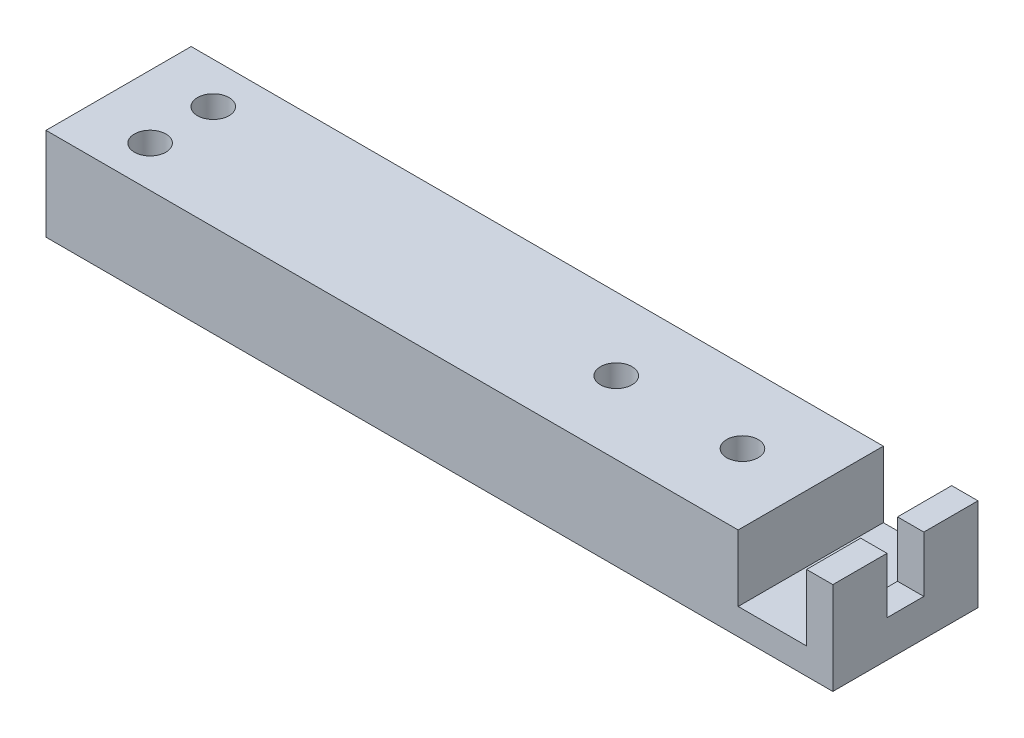
SolidWorks part; units mm, degrees
ref_plane "Front Plane" through (0, 0, 0) normal (0, 0, 1) x (1, 0, 0)
ref_plane "Top Plane" through (0, 0, 0) normal (0, 1, 0) x (1, 0, 0)
ref_plane "Right Plane" through (0, 0, 0) normal (1, 0, 0) x (0, 0, -1)
sketch "Sketch1" plane through (0, 0, 0) normal (0, 1, 0) x (1, 0, 0)
  line L1 (-37.4, -6.9) -> (37.4, -6.9)
  line L2 (-37.4, -6.9) -> (-37.4, 6.9)
  line L3 (-37.4, 6.9) -> (37.4, 6.9)
  line L4 (37.4, -6.9) -> (37.4, 6.9)
  line L5 (-37.4, -6.9) -> (37.4, 6.9) construction
  line L6 (-37.4, 6.9) -> (37.4, -6.9) construction
  point P0 (0, 0)
  dimension "D1" = 13.8
  dimension "D2" = 74.8
extrude "Boss-Extrude1" add sketch "Sketch1" along normal blind 8.8
sketch "Sketch2" plane through (0, 8.8, 0) normal (0, 1, 0) x (1, 0, 0)
  line L0 (-37.4, -6.9) -> (37.4, -6.9) construction
  line L1 (34.9, -6.9) -> (28.4, -6.9)
  line L2 (34.9, -6.9) -> (34.9, 6.9)
  line L3 (34.9, 6.9) -> (28.4, 6.9)
  line L4 (28.4, -6.9) -> (28.4, 6.9)
  line L5 (37.4, 6.9) -> (-37.4, 6.9) construction
  line L6 (37.4, -6.9) -> (37.4, 6.9) construction
  dimension "D1" = 2.5
  dimension "D2" = 6.5
extrude "Cut-Extrude1" cut sketch "Sketch2" against normal offset from surface (6.3 mm away) 2.5 up to face at (0, 0, 0)
sketch "Sketch3" plane through (37.4, 0, 0) normal (1, 0, 0) x (0, 0, -1)
  line L0 (-6.9, 8.8) -> (6.9, 8.8) construction
  line L1 (1.75, 8.8) -> (-1.75, 8.8)
  line L2 (1.75, 8.8) -> (1.75, 3.5)
  line L3 (1.75, 3.5) -> (-1.75, 3.5)
  line L4 (-1.75, 8.8) -> (-1.75, 3.5)
  line L5 (-6.9, 0) -> (6.9, 0) construction
  point P8 (0, 0)
  point P9 (0, 8.8)
  dimension "D1" = 3.5
  dimension "D2" = 3.5
extrude "Cut-Extrude2" cut sketch "Sketch3" against normal blind 2.8
sketch "Sketch4" plane through (0, 8.8, 0) normal (0, 1, 0) x (1, 0, 0)
  line L0 (-37.4, 6.9) -> (-37.4, -6.9) construction
  line L1 (28.4, 6.9) -> (28.4, -6.9) construction
  circle A0 centre (21.91, 0) radius 1.5
  circle A1 centre (9.91, 0) radius 1.5
  point P6 (-37.4, 0)
  dimension "D1" = 3
  dimension "D2" = 6.49
  dimension "D3" = 12
extrude "Cut-Extrude3" cut sketch "Sketch4" against normal blind 7
sketch "Sketch5" plane through (0, 8.8, 0) normal (0, 1, 0) x (1, 0, 0)
  line L0 (-31.4, 3) -> (-31.4, -3) construction
  line L1 (-37.4, 6.9) -> (-37.4, -6.9) construction
  circle A0 centre (-31.4, 3) radius 1.5
  circle A1 centre (-31.4, -3) radius 1.5
  point P6 (-37.4, 0)
  point P7 (-31.4, 0)
  dimension "D2" = 3
  dimension "D1" = 6
  dimension "D3" = 6
extrude "Cut-Extrude4" cut sketch "Sketch5" against normal through all both and the other way through all
